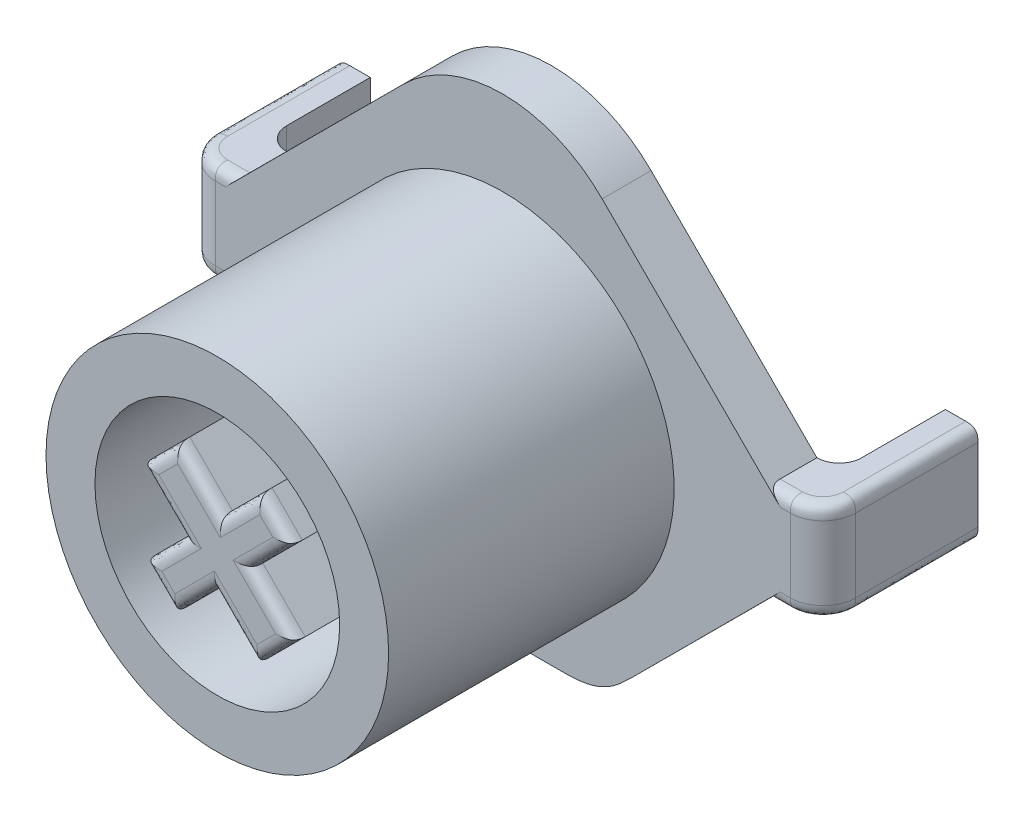
SolidWorks part; units mm, degrees
ref_plane "Front Plane" through (0, 0, 0) normal (0, 0, 1) x (1, 0, 0)
ref_plane "Top Plane" through (0, 0, 0) normal (0, 1, 0) x (1, 0, 0)
ref_plane "Right Plane" through (0, 0, 0) normal (1, 0, 0) x (0, 0, -1)
sketch "Cherry" plane through (0, 0, 0) normal (0, 0, 1) x (1, 0, 0)
  line L0 (-0.8132, -0.0707) -> (-1.8562, 0.9723)
  line L1 (0.9723, -1.8562) -> (-0.0707, -0.8132)
  line L2 (0.9723, -1.8562) -> (1.8562, -0.9723)
  line L3 (1.8562, -0.9723) -> (0.8132, 0.0707)
  line L4 (-1.8562, 0.9723) -> (-0.9723, 1.8562)
  line L6 (0.0707, 0.8132) -> (-0.9723, 1.8562)
  line L7 (-1.043, -1.7854) -> (-1.7854, -1.043)
  line L8 (-1.043, -1.7854) -> (-0.0707, -0.8132)
  line L9 (1.7854, 1.043) -> (1.043, 1.7854)
  line L10 (-1.7854, -1.043) -> (-0.8132, -0.0707)
  line L15 (0.8132, 0.0707) -> (1.7854, 1.043)
  line L18 (0.0707, 0.8132) -> (1.043, 1.7854)
  circle A0 centre (0, 0) radius 3
  circle A1 centre (0, 0) radius 4.2
extrude "Outer Cylinder" add sketch "Cherry" along normal blind 7 contours L18 L6 L4 L0 L10 L7 L8 L1 L2 L3 L15 L9 | A1 A0 region at (0, 0, 0) region at (-4.0812, 0, 0)
sketch "Inner Gap" plane through (0, 0, 0) normal (0, 0, 1) x (1, 0, 0)
  line L0 (-1.8562, 0.9723) -> (-2.8284, 0)
  line L1 (-1.043, -1.7854) -> (-0.0707, -0.8132)
  line L2 (-0.9723, 1.8562) -> (0.0707, 0.8132)
  line L3 (-0.8132, -0.0707) -> (-1.7854, -1.043)
  line L4 (0.9723, -1.8562) -> (0, -2.8284)
  line L11 (-0.9723, 1.8562) -> (0, 2.8284)
  line L13 (0, 2.8284) -> (1.043, 1.7854)
  line L15 (0.8132, 0.0707) -> (1.7854, 1.043)
  line L16 (1.7854, 1.043) -> (2.8284, 0)
  line L17 (0.8132, 0.0707) -> (1.8562, -0.9723)
  line L18 (0.0707, 0.8132) -> (1.043, 1.7854)
  line L19 (2.8284, 0) -> (1.8562, -0.9723)
  line L20 (0.9723, -1.8562) -> (-0.0707, -0.8132)
  line L23 (0, -2.8284) -> (-1.043, -1.7854)
  line L25 (-1.7854, -1.043) -> (-2.8284, 0)
  line L26 (-0.8132, -0.0707) -> (-1.8562, 0.9723)
  circle A0 centre (0, 0) radius 3
sketch "Base Shape" plane through (0, 0, 0) normal (0, 0, 1) x (1, 0, 0)
  line L0 (-1.8562, 0.9723) -> (-2.8284, 0)
  line L1 (-1.043, -1.7854) -> (-0.0707, -0.8132)
  line L2 (-0.9723, 1.8562) -> (0.0707, 0.8132)
  line L3 (-0.8132, -0.0707) -> (-1.7854, -1.043)
  line L4 (0.9723, -1.8562) -> (0, -2.8284)
  line L5 (0, 0) -> (50000, 0) construction
  line L6 (0, -1000) -> (0, 49000) construction
  line L7 (-7.85, 0) -> (-7.85, -50000) construction
  line L8 (7.85, 0) -> (7.85, -50000) construction
  line L9 (-1000, 1.2) -> (49000, 1.2) construction
  line L10 (-1000, -1.2) -> (49000, -1.2) construction
  line L11 (-0.9723, 1.8562) -> (0, 2.8284)
  line L12 (-6.5, -1000) -> (-6.5, 49000) construction
  line L13 (0, 2.8284) -> (1.043, 1.7854)
  line L14 (6.5, -1000) -> (6.5, 49000) construction
  line L15 (0.8132, 0.0707) -> (1.7854, 1.043)
  line L16 (1.7854, 1.043) -> (2.8284, 0)
  line L17 (0.8132, 0.0707) -> (1.8562, -0.9723)
  line L18 (0.0707, 0.8132) -> (1.043, 1.7854)
  line L19 (2.8284, 0) -> (1.8562, -0.9723)
  line L20 (0.9723, -1.8562) -> (-0.0707, -0.8132)
  line L21 (-713.6068, -705.9068) -> (34641.7323, 34649.4323) construction
  line L22 (-700.6068, -708.3068) -> (34654.7323, 34647.0323) construction
  line L23 (0, -2.8284) -> (-1.043, -1.7854)
  line L24 (-713.6068, 705.9068) -> (34641.7323, -34649.4323) construction
  line L25 (-1.7854, -1.043) -> (-2.8284, 0)
  line L26 (-0.8132, -0.0707) -> (-1.8562, 0.9723)
  line L27 (-700.6068, 708.3068) -> (34654.7323, -34647.0323) construction
  line L28 (-6.5, -1.2) -> (-6.5, 1.2)
  line L29 (-6.5, 1.2) -> (-2.4358, 5.2642)
  line L30 (-706.0638, 708.8922) -> (34649.2753, -34646.4468) construction
  line L31 (-708.8922, 706.0638) -> (34646.4468, -34649.2753) construction
  line L32 (-708.0791, -705.2506) -> (34647.26, 34650.0884) construction
  line L33 (-705.2506, -708.0791) -> (34650.0884, 34647.26) construction
  line L35 (2.4358, 5.2642) -> (6.5, 1.2)
  line L36 (6.5, 1.2) -> (6.5, -1.2)
  line L37 (6.5, -1.2) -> (2.4358, -5.2642)
  line L38 (2.4358, -5.2642) -> (-2.4358, -5.2642)
  line L39 (-2.4358, -5.2642) -> (-6.5, -1.2)
  arc A0 (-2.4358, 5.2642) -> (2.4358, 5.2642) centre (0, 2.8284) cw
  dimension "D1" = 7.85
  dimension "D2" = 1.2
  dimension "D3" = 1.35
extrude "Inner Wall" add sketch "Inner Gap" along normal blind 3
extrude "Base" add sketch "Base Shape" against normal blind 1.2
sketch "Stand Shape" plane through (0, 0, 0) normal (0, 1, 0) x (1, 0, 0)
  line L0 (-1000, 0) -> (49000, 0) construction
  line L1 (-1000.3818, 3.8) -> (48999.6182, 3.8) construction
  line L2 (-7.85, -1001.4882) -> (-7.85, 48998.5118) construction
  line L3 (0, -1000) -> (0, 49000) construction
  line L4 (-6.5, -997.4352) -> (-6.5, 49002.5648) construction
  line L5 (6.5, -997.4352) -> (6.5, 49002.5648) construction
  line L6 (7.85, -1001.4882) -> (7.85, 48998.5118) construction
  line L7 (-7.05, -998.4603) -> (-7.05, 49001.5397) construction
  line L8 (6.5, 0) -> (7.05, 0)
  line L9 (6.5, 1.2) -> (6.5, 0)
  line L10 (-1021.5655, 1.2) -> (48978.4345, 1.2) construction
  line L11 (-7.85, 3.8) -> (-7.05, 3.8)
  line L12 (-7.05, 3.8) -> (-7.05, 1.75)
  line L13 (7.05, 3.8) -> (7.05, 1.75)
  line L14 (-6.5, 1.2) -> (-6.5, 0)
  line L15 (-6.5, 0) -> (-7.05, 0)
  line L16 (7.85, 3.8) -> (7.05, 3.8)
  line L17 (-7.85, 3.8) -> (-7.85, 0.8)
  line L18 (7.85, 3.8) -> (7.85, 0.8)
  arc A0 (-7.85, 0.8) -> (-7.05, 0) centre (-7.05, 0.8) ccw
  arc A1 (-7.05, 1.75) -> (-6.5, 1.2) centre (-6.5, 1.75) ccw
  arc A2 (7.85, 0.8) -> (7.05, 0) centre (7.05, 0.8) cw
  arc A3 (7.05, 1.75) -> (6.5, 1.2) centre (6.5, 1.75) cw
  dimension "D1" = 3.8
  dimension "D2" = 7.85
  dimension "D3" = 1.35
  dimension "D4" = 0.8
  dimension "D6" = 1.2
extrude "Stand" add sketch "Stand Shape" along normal mid plane 2.4
fillet "Fillet1" radius 2.5 2 edges at (2.4358, -5.2642, -0.6) (-2.4358, -5.2642, -0.6) curvature continuous yes
fillet "Fillet2" radius 0.3 12 edges at (-1.4142, 1.4142, 7) (-1.3347, 0.4508, 7) (-1.2993, -0.5568, 7) (-1.4142, -1.4142, 7) (-0.5568, -1.2993, 7) (0.4508, -1.3347, 7) (1.4142, -1.4142, 7) (1.3347, -0.4508, 7) (-0.4508, 1.3347, 7) (0.5568, 1.2993, 7) (1.4142, 1.4142, 7) (1.2993, 0.5568, 7) curvature continuous yes
fillet "Fillet3" radius 0.3 12 edges at (-6.775, -1.2, 0) (-7.6157, -1.2, -0.2343) (-6.775, 1.2, 0) (-7.6157, 1.2, -0.2343) (6.775, -1.2, 0) (7.6157, -1.2, -0.2343) (6.775, 1.2, 0) (7.6157, 1.2, -0.2343) (-7.85, -1.2, -2.3) (-7.85, 1.2, -2.3) (7.85, -1.2, -2.3) (7.85, 1.2, -2.3) curvature continuous yes
